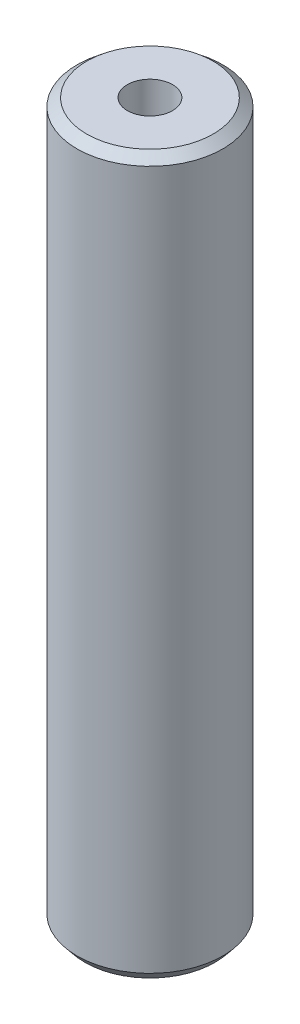
SolidWorks part; units mm, degrees
ref_plane "Front Plane" through (0, 0, 0) normal (0, 0, 1) x (1, 0, 0)
ref_plane "Top Plane" through (0, 0, 0) normal (0, 1, 0) x (1, 0, 0)
ref_plane "Right Plane" through (0, 0, 0) normal (1, 0, 0) x (0, 0, -1)
sketch "Sketch1" plane through (0, 0, 0) normal (0, 1, 0) x (1, 0, 0)
  circle A0 centre (0, 0) radius 40
  dimension "SHAFT_OD" = 80
extrude "Boss-Extrude1" add sketch "Sketch1" along normal blind 393.1516
sketch "Sketch2" plane through (0, 0, 0) normal (0, 1, 0) x (1, 0, 0)
  circle A0 centre (0, 0) radius 12.3962
  dimension "BORE_D" = 24.7924
extrude "Cut-Extrude1" cut sketch "Sketch2" along normal through all
chamfer "Chamfer1" distance 4.3736 angle 50.53 2 edges at (0, 393.1516, 40) (0, 0, 40) first distance on face at (0, 393.1516, 40) first distance on face at (0, 0, 12.3962)
